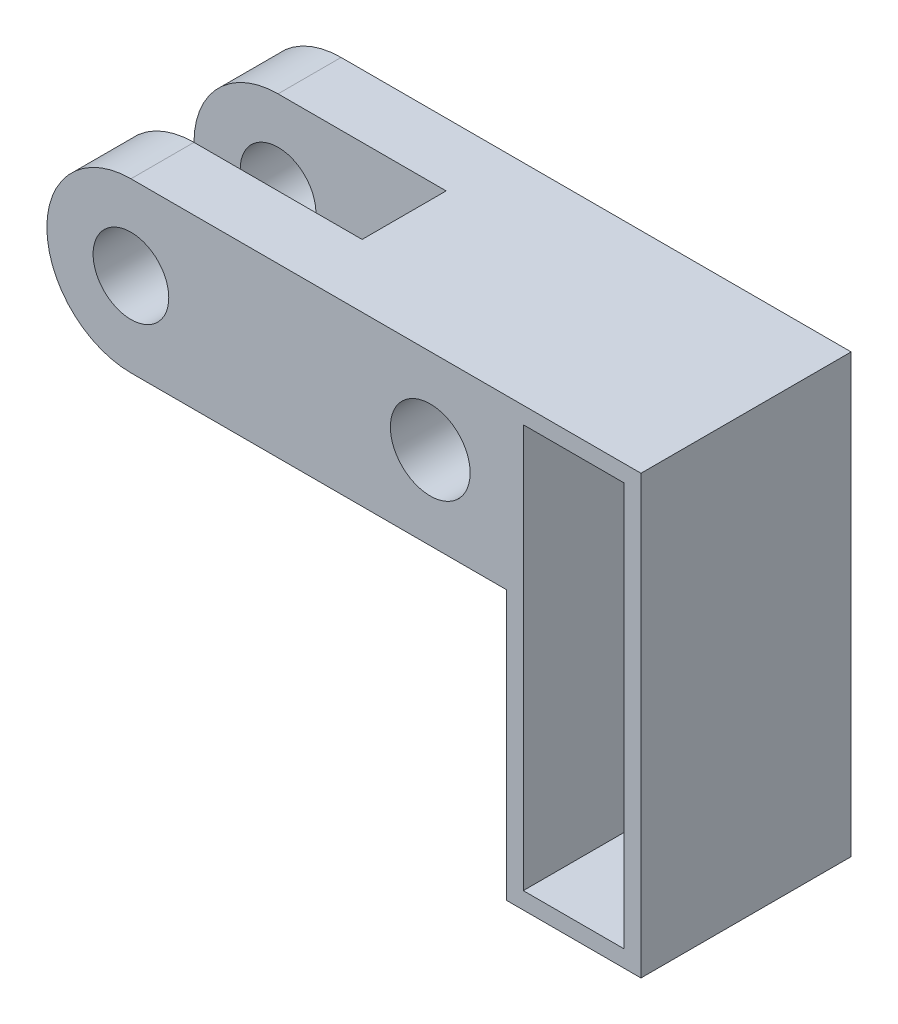
SolidWorks part; units mm, degrees
ref_plane "Front Plane" through (0, 0, 0) normal (0, 0, 1) x (1, 0, 0)
ref_plane "Top Plane" through (0, 0, 0) normal (0, 1, 0) x (1, 0, 0)
ref_plane "Right Plane" through (0, 0, 0) normal (1, 0, 0) x (0, 0, -1)
sketch "Sketch1" plane through (0, 0, 0) normal (0, 0, 1) x (1, 0, 0)
  line L0 (0, -5) -> (22.3365, -5)
  line L1 (0, 5) -> (30.3365, 5)
  line L10 (30.3365, 5) -> (30.3365, -21)
  line L11 (30.3365, -21) -> (22.3365, -21)
  line L12 (22.3365, -5) -> (22.3365, -21)
  line L14 (23.3365, -20) -> (29.3365, -20)
  line L15 (23.3365, -20) -> (23.3365, 4)
  line L16 (23.3365, 4) -> (29.3365, 4)
  line L17 (29.3365, -20) -> (29.3365, 4)
  arc A0 (0, 5) -> (0, -5) centre (0, 0) ccw
  circle A2 centre (0, 0) radius 2.25
  circle A4 centre (17.8029, -0.0668) radius 2.3727
  dimension "D1" = 5
  dimension "D3" = 4.5
  dimension "D4" = 1
  dimension "D5" = 1
  dimension "D6" = 1
  dimension "D7" = 6
  dimension "D8" = 24
  dimension "D9" = 1
extrude "Boss-Extrude1" add sketch "Sketch1" along normal mid plane 12.5 contours L1 A0 A2 region at (12.9057, -1.7431, 0)
sketch "Sketch13" plane through (0, -5, 0) normal (0, -1, 0) x (1, 0, 0)
  line L0 (-5, 6.25) -> (-5, -6.25) construction
  line L1 (-5, -2.5) -> (10, -2.5)
  line L2 (-5, -2.5) -> (-5, 2.5)
  line L3 (-5, 2.5) -> (10, 2.5)
  line L4 (10, -2.5) -> (10, 2.5)
  point P6 (-5, 0)
  dimension "D1" = 5
  dimension "D2" = 15
extrude "Cut-Extrude1" cut sketch "Sketch13" against normal blind 10
chamfer "Chamfer1" distance 5 distance2 10 1 edges at (10, -5, 0) tangent propagation no first distance on face at (8.0841, -5, 0)
